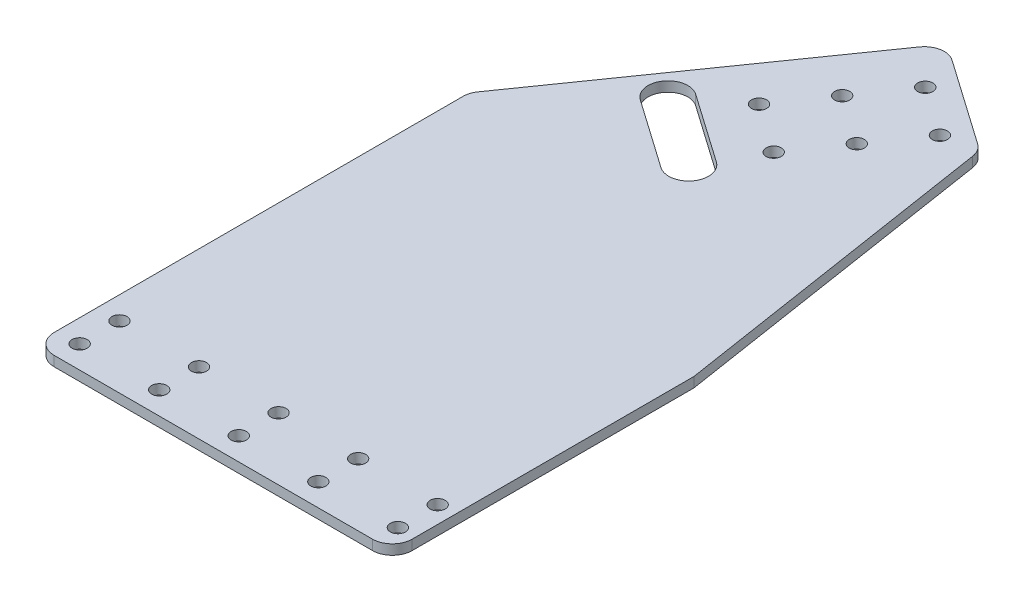
SolidWorks part; units mm, degrees
ref_plane "Front Plane" through (0, 0, 0) normal (0, 0, 1) x (1, 0, 0)
ref_plane "Top Plane" through (0, 0, 0) normal (0, 1, 0) x (1, 0, 0)
ref_plane "Right Plane" through (0, 0, 0) normal (1, 0, 0) x (0, 0, -1)
sketch "Sketch1" plane through (0, 0, 0) normal (0, 1, 0) x (1, 0, 0)
  line L5 (0, 0) -> (114.3, 0)
  line L6 (0, 0) -> (0, 228.6)
  line L7 (0, 228.6) -> (114.3, 228.6)
  line L8 (114.3, 0) -> (114.3, 228.6)
  dimension "D1" = 228.6
  dimension "D2" = 114.3
extrude "Boss-Extrude1" add sketch "Sketch1" along normal blind 3.175
sketch "Sketch2" plane through (0, 3.175, 0) normal (0, 1, 0) x (1, 0, 0)
  line L0 (0, 0) -> (114.3, 0) construction
  line L1 (0, 228.6) -> (0, 0) construction
  circle A0 centre (7.239, 7.239) radius 2.413
  circle A2 centre (7.239, 19.939) radius 2.413
  circle A3 centre (32.639, 19.939) radius 2.413
  circle A4 centre (58.039, 19.939) radius 2.413
  circle A5 centre (83.439, 19.939) radius 2.413
  circle A6 centre (108.839, 19.939) radius 2.413
  circle A7 centre (32.639, 7.239) radius 2.413
  circle A8 centre (58.039, 7.239) radius 2.413
  circle A9 centre (83.439, 7.239) radius 2.413
  circle A10 centre (108.839, 7.239) radius 2.413
  dimension "D1" = 4.826
  dimension "D2" = 7.239
  dimension "D3" = 7.239
  dimension "D4" = 2
  dimension "D5" = 5
extrude "Cut-Extrude1" cut sketch "Sketch2" against normal through all
sketch "Sketch3" plane through (0, 0, 0) normal (0, -1, 0) x (1, 0, 0)
  line L0 (71.2693, -213.168) -> (23.3684, -144.7584) construction
  line L1 (71.2693, -213.168) -> (100.677, -192.5765) construction
  line L2 (23.3684, -144.7584) -> (52.7761, -124.1669) construction
  line L3 (100.677, -192.5765) -> (52.7761, -124.1669) construction
  line L4 (0, -228.6) -> (0, 0) construction
  circle A0 centre (71.2693, -213.168) radius 2.413
  circle A6 centre (60.3427, -197.5632) radius 2.413
  circle A7 centre (49.4161, -181.9583) radius 2.413
  circle A8 centre (75.9475, -186.6365) radius 2.413
  circle A9 centre (65.0209, -171.0317) radius 2.413
  circle A10 centre (86.8742, -202.2414) radius 2.413
  point P7 (71.6652, -192.7887)
  point P8 (17.9704, -148.5381)
  point P9 (71.2693, -213.168)
  dimension "D4" = 4.826
  dimension "D1" = 35
  dimension "D3" = 3
  dimension "D2" = 2
extrude "Cut-Extrude2" cut sketch "Sketch3" against normal through all
sketch "Sketch4" plane through (0, 0, 0) normal (0, -1, 0) x (1, 0, 0)
  line L0 (62.8285, -228.6) -> (0, -138.8716)
  line L1 (114.3, -228.6) -> (0, -228.6) construction
  line L2 (62.8285, -228.6) -> (0, -228.6)
  line L3 (0, -228.6) -> (0, -138.8716)
  line L4 (62.8285, -228.6) -> (114.3, -192.5593)
  line L6 (114.3, 0) -> (114.3, -228.6) construction
  line L7 (114.3, -192.5593) -> (114.3, -228.6)
  line L8 (114.3, -228.6) -> (62.8285, -228.6)
  line M20 (0, 0) -> (0, -228.6)
  line M21 (0, -228.6) -> (114.3, -228.6)
  line M22 (114.3, -228.6) -> (114.3, 0)
  dimension "D1" = 35
  dimension "D3" = 89.7284
extrude "Cut-Extrude3" cut sketch "Sketch4" against normal through all contours L4 M21 M22 | L0 M21 M20 region at (20.9428, 0, -198.6905) region at (97.1428, 0, -216.5864)
sketch "Sketch5" plane through (0, 0, 0) normal (0, -1, 0) x (1, 0, 0)
  line L0 (97.4773, -204.3387) -> (114.3, -96.2796)
  line L1 (62.8285, -228.6) -> (114.3, -192.5593) construction
  line L3 (97.4773, -204.3387) -> (114.3, -192.5593)
  line L4 (114.3, -192.5593) -> (114.3, -96.2796)
extrude "Cut-Extrude4" cut sketch "Sketch5" against normal through all
sketch "Sketch6" plane through (0, 0, 0) normal (0, -1, 0) x (1, 0, 0)
  line L0 (54.9446, -153.9639) -> (32.8898, -169.4069) construction
  line L1 (58.5868, -159.1656) -> (36.532, -174.6085)
  line L2 (51.3024, -148.7623) -> (29.2476, -164.2053)
  line L3 (62.8285, -228.6) -> (0, -138.8716) construction
  line L4 (62.8285, -228.6) -> (97.4773, -204.3387) construction
  arc A0 (58.5868, -159.1656) -> (51.3024, -148.7623) centre (54.9446, -153.9639) ccw
  arc A1 (29.2476, -164.2053) -> (36.532, -174.6085) centre (32.8898, -169.4069) ccw
  point P2 (43.9172, -161.6854)
  point P7 (32.5276, -169.7716)
  point P8 (0, 0)
  point P9 (61.0408, -150.6184)
  point P10 (32.5393, -169.8083)
  point P11 (60.808, -150.8514)
  point P12 (0, 0)
  point P13 (54.9436, -153.9625)
  dimension "D1" = 26.924
  dimension "D2" = 12.7
  dimension "D3" = 9.4274
  dimension "D4" = 65.6603
extrude "Cut-Extrude5" cut sketch "Sketch6" against normal through all
fillet "Fillet1" radius 6.35 5 edges at (0, 1.5875, -138.8716) (97.4773, 1.5875, -204.3387) (62.8285, 1.5875, -228.6) (0, 1.5875, 0) (114.3, 1.5875, 0)
